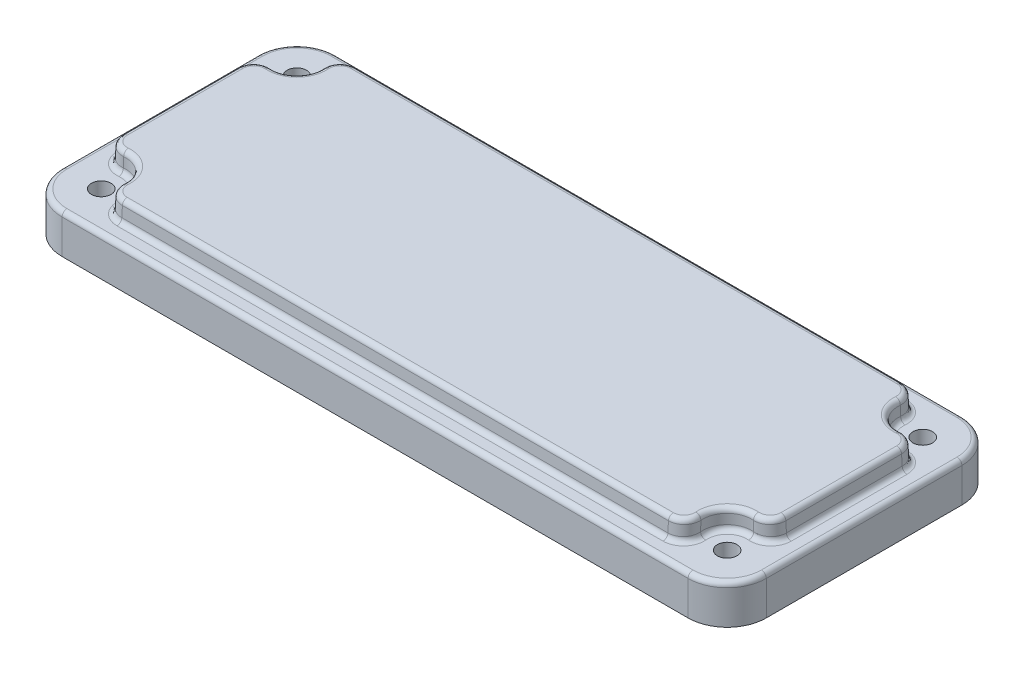
SolidWorks part; units mm, degrees
material "PW20:29:Sc:0:"
ref_plane "Front" through (0, 0, 0) normal (0, 0, 1) x (1, 0, 0)
ref_plane "Top" through (0, 0, 0) normal (0, 1, 0) x (1, 0, 0)
ref_plane "Right" through (0, 0, 0) normal (1, 0, 0) x (0, 0, -1)
sketch "Sketch1" plane through (0, 0, 0) normal (0, 1, 0) x (1, 0, 0)
  line L0 (-50.8, 22.225) -> (50.8, 22.225)
  line L1 (-57.15, 15.875) -> (-57.15, -15.875)
  line L2 (50.8, -22.225) -> (-50.8, -22.225)
  line L3 (57.15, -15.875) -> (57.15, 15.875)
  line L4 (-50.8, -15.875) -> (50.8, 15.875) construction
  arc A0 (-57.15, -15.875) -> (-50.8, -22.225) centre (-50.8, -15.875) ccw
  arc A1 (57.15, -15.875) -> (50.8, -22.225) centre (50.8, -15.875) cw
  arc A2 (50.8, 22.225) -> (57.15, 15.875) centre (50.8, 15.875) cw
  arc A3 (-50.8, 22.225) -> (-57.15, 15.875) centre (-50.8, 15.875) ccw
  dimension "D1" = 114.3
  dimension "D2" = 44.45
  dimension "D4" = 6.35
extrude "Base-Extrude" add sketch "Sketch1" along normal blind 6.35
sketch "Sketch2" plane through (0, 6.35, 0) normal (0, 1, 0) x (-1, 0, 0)
  line L4 (50.8, 19.05) -> (-50.8, 19.05)
  line L5 (-53.975, 15.875) -> (-53.975, -15.875)
  line L6 (-50.8, -19.05) -> (50.8, -19.05)
  line L7 (53.975, -15.875) -> (53.975, 15.875)
  line L8 (50.8, 19.05) -> (-50.8, 19.05)
  line L9 (-53.975, 15.875) -> (-53.975, -15.875)
  line L10 (-50.8, -19.05) -> (50.8, -19.05)
  line L11 (53.975, -15.875) -> (53.975, 15.875)
  arc A4 (53.975, 15.875) -> (50.8, 19.05) centre (50.8, 15.875) ccw
  arc A5 (53.975, 15.875) -> (50.8, 19.05) centre (50.8, 15.875) ccw
  arc A6 (-50.8, 19.05) -> (-53.975, 15.875) centre (-50.8, 15.875) ccw
  arc A7 (-50.8, 19.05) -> (-53.975, 15.875) centre (-50.8, 15.875) ccw
  arc A8 (-53.975, -15.875) -> (-50.8, -19.05) centre (-50.8, -15.875) ccw
  arc A9 (-53.975, -15.875) -> (-50.8, -19.05) centre (-50.8, -15.875) ccw
  arc A10 (50.8, -19.05) -> (53.975, -15.875) centre (50.8, -15.875) ccw
  arc A11 (50.8, -19.05) -> (53.975, -15.875) centre (50.8, -15.875) ccw
  dimension "D1" = 3.175
extrude "Boss-Extrude1" add sketch "Sketch2" along normal blind 3.175 draft 3
sketch "Sketch3" plane through (0, 9.525, 0) normal (0, 1, 0) x (-1, 0, 0)
  circle A0 centre (-50.8, 15.875) radius 3.9687
  dimension "D1" = 7.9375
extrude "Cut-Extrude1" cut sketch "Sketch3" against normal up to surface (3.175 mm away)
sketch "Sketch4" plane through (0, 6.35, 0) normal (0, 1, 0) x (-1, 0, 0)
  circle A0 centre (-50.8, 15.875) radius 1.5875
  dimension "D1" = 3.175
extrude "Cut-Extrude2" cut sketch "Sketch4" against normal through all
mirror "Mirror1" about plane through (0, 0, 0) normal (0, 0, 1) of "Cut-Extrude2", "Cut-Extrude1"
mirror "Mirror2" about plane through (0, 0, 0) normal (1, 0, 0) of "Mirror1", "Cut-Extrude1", "Cut-Extrude2"
fillet "Fillet1" radius 2.54 8 edges at (53.8935, 7.9044, 13.3888) (48.3138, 7.9044, 18.9685) (53.8935, 7.9044, -13.3888) (48.3138, 7.9044, -18.9685) (-53.8935, 7.9044, -13.3888) (-48.3138, 7.9044, -18.9685) (-48.3138, 7.9044, 18.9685) (-53.8935, 7.9044, 13.3888)
fillet "Fillet2" radius 0.7937 56 edges at (55.2901, 6.35, 20.3651) (0, 6.35, 19.05) (0, 9.525, 18.8836) (-44.315, 7.9366, 18.9668) (44.315, 7.9366, 18.9668) (-53.8086, 9.525, 0) (-47.9937, 9.525, 13.0687) (47.9937, 9.525, 13.0687) (53.8086, 9.525, 0) (47.9937, 9.525, -13.0687) (0, 9.525, -18.8836) (-47.9937, 9.525, -13.0687) (-46.3986, 9.525, 17.785) (-53.2526, 9.525, 10.9683) (-52.71, 9.525, -11.4736) (-45.8933, 9.525, -18.3276) (46.3986, 9.525, -17.785) (53.2526, 9.525, -10.9683) (52.71, 9.525, 11.4736) (45.8933, 9.525, 18.3276) (47.9937, 6.35, 13.0687) (51.1344, 7.9366, 11.9204) (46.8454, 7.9366, 16.2094) (53.975, 6.35, 0) (53.8918, 7.9366, -9.39) (53.8918, 7.9366, 9.39) (47.9937, 6.35, -13.0687) (46.8454, 7.9366, -16.2094) (51.1344, 7.9366, -11.9204) (0, 6.35, -19.05) (-44.315, 7.9366, -18.9668) (44.315, 7.9366, -18.9668) (-47.9937, 6.35, -13.0687) (-51.1344, 7.9366, -11.9204) (-46.8454, 7.9366, -16.2094) (-53.975, 6.35, 0) (57.15, 6.35, 0) (-53.8918, 7.9366, 9.39) (-53.8918, 7.9366, -9.39) (-47.9937, 6.35, 13.0687) (-46.8454, 7.9366, 16.2094) (-51.1344, 7.9366, 11.9204) (46.2919, 6.35, 18.1127) (53.2408, 6.35, 11.1827) (53.0648, 6.35, -11.3446) (46.1444, 6.35, -18.2787) (-46.2625, 6.35, -18.1482) (-53.2213, 6.35, -11.2022) (-53.0383, 6.35, 11.3664) (-46.1066, 6.35, 18.3169) (55.2901, 6.35, -20.3651) (0, 6.35, -22.225) (-55.2901, 6.35, -20.3651) (-57.15, 6.35, 0) (-55.2901, 6.35, 20.3651) (0, 6.35, 22.225)
sketch "Sketch5" plane through (0, 0, 0) normal (0, -1, 0) x (1, 0, 0)
  line L0 (-44.45, 15.875) -> (44.45, 15.875)
  line L1 (-44.45, 15.875) -> (-44.45, -15.875)
  line L2 (44.45, -15.875) -> (-44.45, -15.875)
  line L3 (44.45, -15.875) -> (44.45, 15.875)
  line L4 (50.8, 22.225) -> (-50.8, 22.225) construction
  line L5 (57.15, 15.875) -> (57.15, -15.875) construction
  line L6 (-57.15, -15.875) -> (-57.15, 15.875) construction
  line L7 (-50.8, -22.225) -> (50.8, -22.225) construction
  dimension "D1" = 6.35
  dimension "D2" = 12.7
  dimension "D3" = 12.7
  dimension "D4" = 6.35
extrude "Cut-Extrude3" cut sketch "Sketch5" against normal blind 6.35 draft 3
fillet "Fillet3" radius 6.35 4 edges at (-44.2836, 3.175, -15.7086) (-44.2836, 3.175, 15.7086) (44.2836, 3.175, 15.7086) (44.2836, 3.175, -15.7086)
fillet "Fillet4" radius 3.175 8 edges at (-44.1172, 6.35, 0) (0, 6.35, 15.5422) (0, 6.35, -15.5422) (44.1172, 6.35, 0) (-42.2609, 6.35, -13.6859) (42.2609, 6.35, 13.6859) (42.2609, 6.35, -13.6859) (-42.2609, 6.35, 13.6859)
